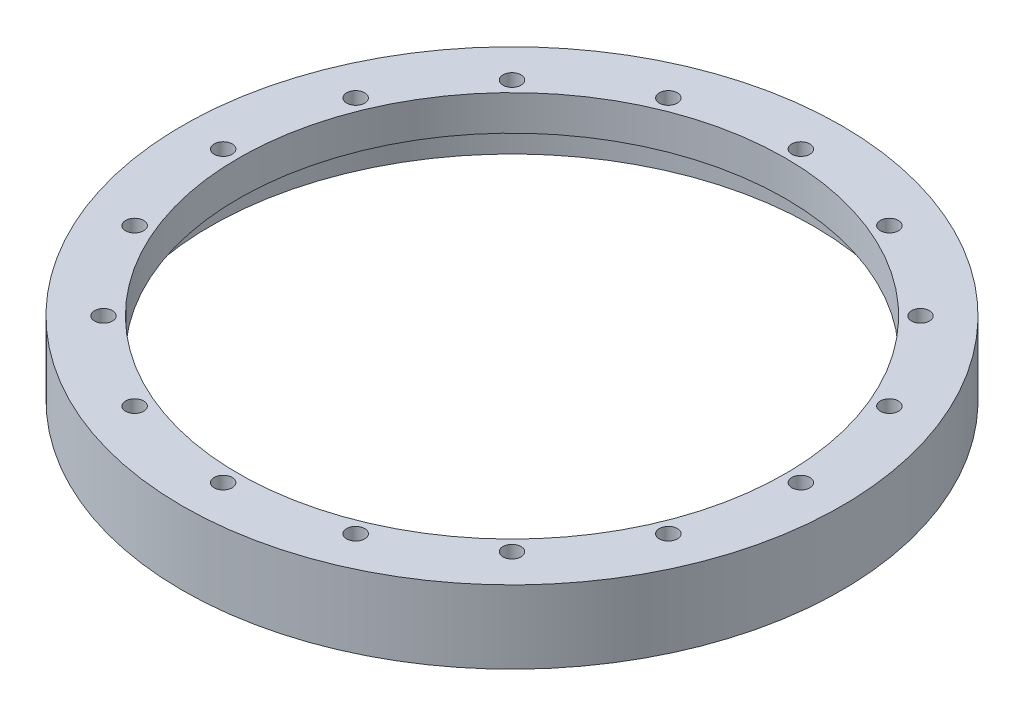
SolidWorks part; units mm, degrees
material "6061-T6 (SS)"
ref_plane "Front Plane" through (0, 0, 0) normal (0, 0, 1) x (1, 0, 0)
ref_plane "Top Plane" through (0, 0, 0) normal (0, 1, 0) x (1, 0, 0)
ref_plane "Right Plane" through (0, 0, 0) normal (1, 0, 0) x (0, 0, -1)
sketch "Sketch1" plane through (0, 0, 0) normal (0, 0, 1) x (1, 0, 0)
  line L0 (-49.4665, 0) -> (-59.6265, 0)
  line L1 (-59.6265, 0) -> (-59.6265, -13.208)
  line L2 (-59.6265, -13.208) -> (-54.5465, -13.208)
  line L3 (-54.5465, -13.208) -> (-54.5465, -6.35)
  line L4 (-54.5465, -6.35) -> (-49.4665, -6.35)
  line L5 (-49.4665, -6.35) -> (-49.4665, 0)
  line L6 (0, 0) -> (0, 8.0765) construction
  dimension "D1" = 49.4665
  dimension "D2" = 54.5465
  dimension "D3" = 5.08
  dimension "D4" = 13.208
  dimension "D5" = 6.35
revolve "Revolve1" add sketch "Sketch1" angle 360 about L6
sketch "Sketch2" plane through (0, 0, 0) normal (0, 1, 0) x (1, 0, 0)
  line L0 (0, 49.4665) -> (0, 52.2605) construction
  circle A0 centre (0, 0) radius 49.4665 construction
  dimension "D1" = 2.794
hole_wizard "#4 Clearance Hole1" positions "3DSketch1" profile "Sketch3" hole size "#4" standard "Ansi Inch"
sketch3d "3DSketch1"
  point P0 (0, 0, -52.2605)
sketch "Sketch3" plane through (0, 0, -52.2605) normal (1, 0, 0) x (0, 0, 1)
  line L0 (0, 0) -> (0, 11.1406)
  line L1 (0, 11.1406) -> (1.6319, 10.16)
  line L2 (1.6319, 10.16) -> (1.6319, 0)
  line L5 (1.6319, 0) -> (0, 0)
  line L10 (0, 11.1406) -> (-1.632, 10.16) construction
  line L11 (0, -6.35) -> (0, 107.95) construction
  dimension "Hole Dia." = 3.2639
  dimension "Hole Depth" = 10.16
  dimension "Drill Angle" = 118
pattern_circular "CirPattern1" count 16 over 360 about axis through (0, 0, 0) along (0, -1, 0) of "#4 Clearance Hole1"
